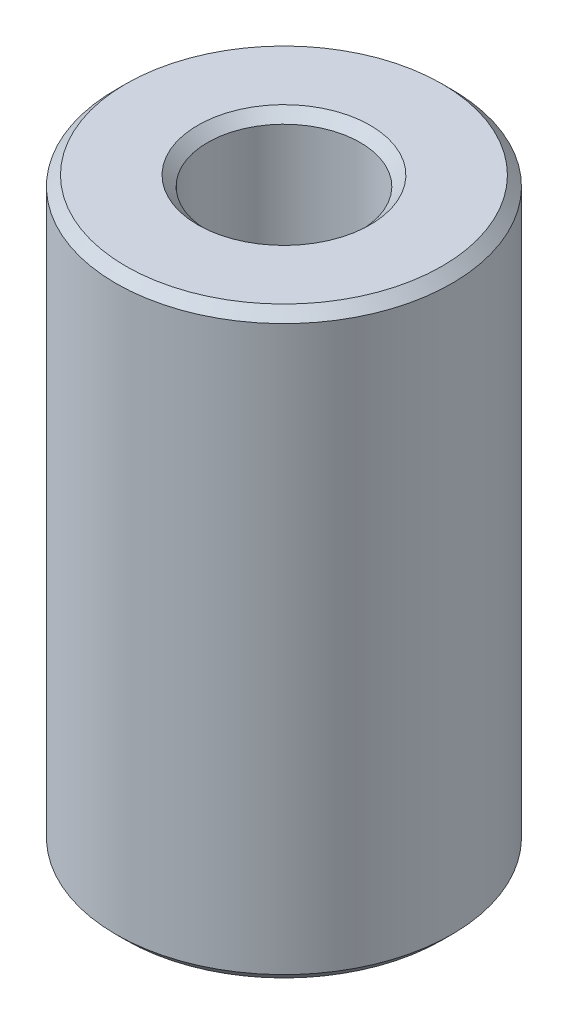
SolidWorks part; units mm, degrees
ref_plane "Front Plane" through (0, 0, 0) normal (0, 0, 1) x (1, 0, 0)
ref_plane "Top Plane" through (0, 0, 0) normal (0, 1, 0) x (1, 0, 0)
ref_plane "Right Plane" through (0, 0, 0) normal (1, 0, 0) x (0, 0, -1)
sketch "Sketch1" plane through (0, 0, 0) normal (0, 1, 0) x (1, 0, 0)
  circle A0 centre (0, 0) radius 5
  dimension "SLEEVE_OD" = 10
extrude "Boss-Extrude1" add sketch "Sketch1" along normal blind 17.3744
sketch "Sketch2" plane through (0, 0, 0) normal (0, 1, 0) x (1, 0, 0)
  circle A0 centre (0, 0) radius 2.2715
  dimension "BORE_D" = 4.543
extrude "Cut-Extrude1" cut sketch "Sketch2" along normal through all
chamfer "Chamfer1" distance 0.2956 angle 45 4 edges at (0, 17.3744, 2.2715) (0, 0, 2.2715) (0, 0, 5) (0, 17.3744, 5)
